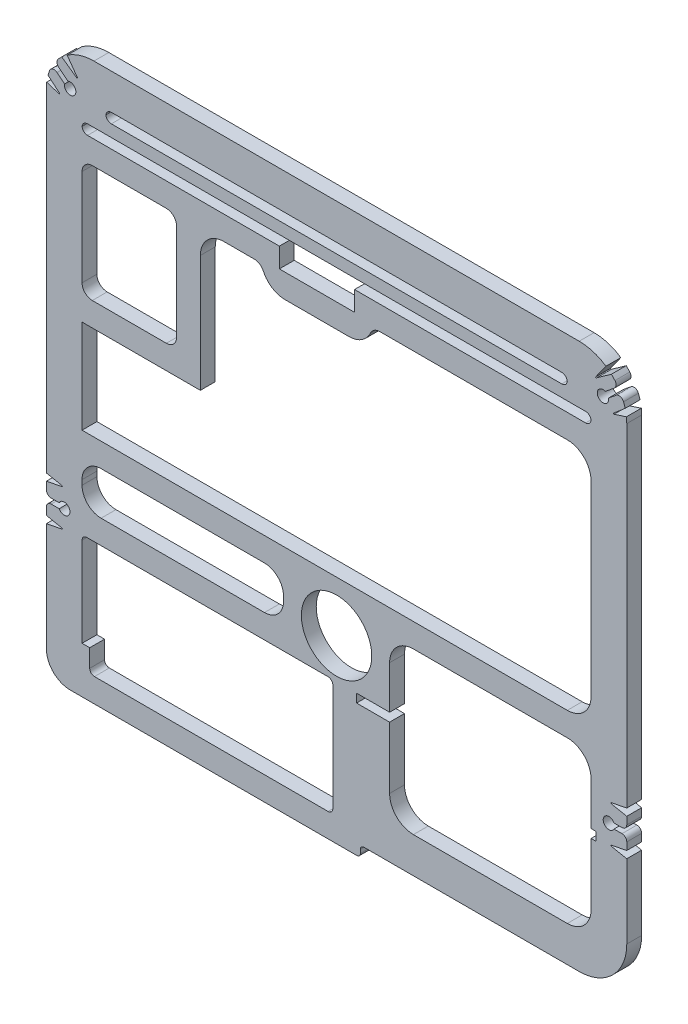
SolidWorks part; units mm, degrees
ref_plane "Front Plane" through (0, 0, 0) normal (0, 0, 1) x (1, 0, 0)
ref_plane "Top Plane" through (0, 0, 0) normal (0, 1, 0) x (1, 0, 0)
ref_plane "Right Plane" through (0, 0, 0) normal (1, 0, 0) x (0, 0, -1)
sketch "Sketch1" plane through (0, 0, 0) normal (0, 0, 1) x (1, 0, 0)
  line L0 (63.9883, 50.6392) -> (63.9883, 46.8292) construction
  line L1 (4.1102, -7.651) -> (66.0868, -7.651)
  line L2 (4.1102, -7.651) -> (4.1102, 50.6392)
  line L3 (4.1102, 50.6392) -> (66.0868, 50.6392)
  line L4 (66.0868, -7.651) -> (66.0868, 50.6392)
  line L5 (62.2768, 46.8292) -> (7.9202, 46.8292)
  line L6 (62.2768, 46.8292) -> (62.2768, -3.841)
  line L7 (62.2768, -3.841) -> (7.9202, -3.841)
  line L8 (7.9202, 46.8292) -> (7.9202, -3.841)
  line L9 (63.9883, 48.7342) -> (18.0707, 48.7342) construction
  line L10 (7.9202, 41.2855) -> (4.1102, 41.2855) construction
  line L11 (6.0152, 41.2855) -> (6.0152, 25.8577) construction
  line L12 (13.5248, -3.841) -> (13.5248, -7.651) construction
  line L13 (13.5248, -5.746) -> (21.1598, -5.746) construction
  line L14 (66.0868, 38.1916) -> (62.2768, 38.1916) construction
  line L15 (64.1818, 38.1916) -> (64.1818, 22.3321) construction
  line L16 (62.2768, 6.192) -> (62.2768, 41.7492) construction
  line L17 (7.9202, 36.7962) -> (7.9202, 1.239) construction
  line L22 (34.9556, 48.7342) -> (35.5018, 48.7342) construction
  line L23 (52.4244, -5.746) -> (51.8782, -5.746) construction
  dimension "D1" = 3.81
  dimension "D2" = 3.81
extrude "Boss-Extrude1" add sketch "Sketch1" along normal blind 1.5875
sketch "Sketch2" plane through (0, 0, 0) normal (0, 0, -1) x (-1, 0, 0)
  line L0 (-62.2768, -3.841) -> (-62.2768, 46.8292) construction
  line L1 (-62.2768, 15.868) -> (-7.9202, 15.868)
  line L2 (-62.2768, 15.868) -> (-62.2768, 13.328)
  line L3 (-62.2768, 13.328) -> (-7.9202, 13.328)
  line L4 (-7.9202, 15.868) -> (-7.9202, 13.328)
  line L5 (-7.9202, 46.8292) -> (-7.9202, -3.841) construction
  line L6 (-13.0532, 15.868) -> (-50.7532, 15.868) construction
  line L8 (-55.2788, 43.4256) -> (-16.9248, 43.4256) construction
  line L9 (-36.3812, 41.3174) -> (-29.6248, 41.3174) construction
  line L10 (-36.3812, 43.4256) -> (-36.3812, 41.3174) construction
  line L11 (-62.2768, 43.4256) -> (-37.0162, 43.4256)
  line L12 (-62.2768, 43.4256) -> (-62.2768, 40.8856)
  line L13 (-62.2768, 40.8856) -> (-38.9212, 40.8856)
  line L14 (-7.9202, 43.4256) -> (-7.9202, 40.8856)
  line L15 (-62.2768, 45.7624) -> (-7.9202, 45.7624)
  line L16 (-62.2768, 45.7624) -> (-62.2768, 44.4924)
  line L17 (-62.2768, 44.4924) -> (-7.9202, 44.4924)
  line L18 (-7.9202, 45.7624) -> (-7.9202, 44.4924)
  line L19 (-29.6248, 41.3174) -> (-29.6248, 43.4256) construction
  line L20 (-36.3812, 43.4256) -> (-36.3812, 41.3174) construction
  line L21 (-29.6248, 41.3174) -> (-29.6248, 43.4256) construction
  line L22 (-37.0162, 41.3174) -> (-37.0162, 43.4256)
  line L23 (-28.9898, 41.3174) -> (-37.0162, 41.3174)
  line L24 (-28.9898, 41.3174) -> (-28.9898, 43.4256)
  line L25 (-38.9212, 40.8856) -> (-38.9212, 38.7774)
  line L26 (-38.9212, 38.7774) -> (-27.0848, 38.7774)
  line L27 (-27.0848, 38.7774) -> (-27.0848, 40.8856)
  line L28 (-27.0848, 40.8856) -> (-7.9202, 40.8856)
  line L29 (-28.9898, 43.4256) -> (-7.9202, 43.4256)
  line L30 (-37.0162, 42.249) -> (-36.3812, 42.249) construction
  line L31 (-57.9086, 46.8292) -> (-57.9086, 45.7624) construction
  line L32 (-29.6248, 42.1673) -> (-28.9898, 42.1673) construction
  line L33 (-62.2768, 46.8292) -> (-7.9202, 46.8292) construction
  line L35 (-57.9086, 44.4924) -> (-57.9086, 43.4256) construction
  dimension "D1" = 2.54
  dimension "D2" = 1.905
  dimension "D3" = 2.54
  dimension "D4" = 1.905
  dimension "D5" = 1.27
  dimension "D6" = 0.635
extrude "Boss-Extrude2" add sketch "Sketch2" against normal up to surface (1.5875 mm away) up to face at (35.0985, 21.4941, 1.5875)
sketch "Sketch3" plane through (0, 0, 0) normal (0, 0, -1) x (-1, 0, 0)
  line L1 (-16.3032, 25.868) -> (-7.9202, 25.868) construction
  line L12 (-20.5532, 25.868) -> (-13.0532, 25.868)
  line L13 (-13.0532, 25.868) -> (-7.9202, 25.868)
  line L14 (-7.9202, 40.8856) -> (-7.9202, 15.868) construction
  line L15 (-7.9202, 25.868) -> (-7.9202, 28.408)
  line L16 (-7.9202, 28.408) -> (-18.0132, 28.408)
  line L17 (-18.0132, 28.408) -> (-18.0132, 40.8856)
  line L18 (-27.0848, 40.8856) -> (-7.9202, 40.8856) construction
  line L19 (-18.0132, 40.8856) -> (-20.5532, 40.8856)
  line L20 (-20.5532, 40.8856) -> (-20.5532, 25.868)
  line M27 (-27.0848, 40.8856) -> (-7.9202, 40.8856)
  line M28 (-7.9202, 40.8856) -> (-7.9202, 15.868)
  dimension "D3" = 2.54
  dimension "D4" = 2.54
extrude "Boss-Extrude3" add sketch "Sketch3" against normal up to surface (1.5875 mm away) contours L20 L12 L13 L16 L17 M27 M28 region at (20.3569, 33.3768, 0) up to face at (35.0985, 46.2958, 1.5875)
sketch "Sketch4" plane through (0, 0, 0) normal (0, 0, -1) x (-1, 0, 0)
  line L0 (-62.2768, 13.328) -> (-7.9202, 13.328) construction
  line L1 (-40.7627, 13.328) -> (-29.4343, 13.328)
  line L2 (-40.7627, 13.328) -> (-40.7627, -3.841)
  line L3 (-40.7627, -3.841) -> (-29.4343, -3.841)
  line L4 (-29.4343, 13.328) -> (-29.4343, -3.841)
  line L5 (-7.9202, -3.841) -> (-62.2768, -3.841) construction
  line L6 (-38.8577, 10.4578) -> (-40.7627, 10.4578) construction
  line L7 (-31.3393, 10.4578) -> (-29.4343, 10.4578) construction
  dimension "D1" = 1.905
extrude "Boss-Extrude4" add sketch "Sketch4" against normal up to surface (1.5875 mm away) up to face at (12.9667, 34.6468, 1.5875)
sketch "Sketch5" plane through (0, 0, 0) normal (0, 0, -1) x (-1, 0, 0)
  line L1 (-8.7364, -6.254) -> (-34.6952, -6.254) construction
  line L2 (-8.7364, -6.254) -> (-8.7364, 6.2047) construction
  line L6 (-8.7364, 6.2047) -> (-34.6952, 6.2047) construction
  line L7 (-34.6952, -6.254) -> (-34.6952, 6.2047) construction
  line L8 (-8.7364, -6.254) -> (-34.6952, -6.254)
  line L9 (-8.7364, -6.254) -> (-8.7364, 6.2047)
  line L10 (-8.7364, 6.2047) -> (-34.6952, 6.2047)
  line L11 (-34.6952, -6.254) -> (-34.6952, 6.2047)
  circle A1 centre (-35.0985, 10.4578) radius 3.7592 construction
  circle A2 centre (-35.0985, 10.4578) radius 3.7592
extrude "Cut-Extrude1" cut sketch "Sketch5" against normal up to surface (1.5875 mm away) up to face at (51.5197, 4.7435, 1.5875)
sketch "Sketch10" plane through (0, 0, 1.5875) normal (0, 0, 1) x (1, 0, 0)
  line L0 (29.4343, 13.328) -> (29.4343, 6.2047) construction
  line L1 (7.9202, 6.2047) -> (29.4343, 6.2047)
  line L2 (7.9202, 6.2047) -> (7.9202, 8.7447)
  line L3 (7.9202, 8.7447) -> (29.4343, 8.7447)
  line L4 (29.4343, 6.2047) -> (29.4343, 8.7447)
  line L5 (7.9202, 13.328) -> (7.9202, -3.841) construction
  line L6 (34.6952, 6.2047) -> (29.4343, 6.2047) construction
  dimension "D1" = 2.54
extrude "Boss-Extrude5" add sketch "Sketch10" against normal up to surface (1.5875 mm away) up to face at (20.1965, 2.3595, 0)
fillet "Fillet1" radius 5.08 3 edges at (66.0868, -7.651, 0.7937) (4.1102, 50.6392, 0.7937) (66.0868, 50.6392, 0.7937)
fillet "Fillet2" radius 2.54 5 edges at (20.5532, 40.8856, 0.7937) (27.0848, 38.7774, 0.7937) (62.2768, 40.8856, 0.7937) (62.2768, 15.868, 0.7937) (38.9212, 38.7774, 0.7937)
fillet "Fillet3" radius 1.0922 6 edges at (7.9202, 28.408, 0.7937) (18.0132, 28.408, 0.7937) (7.9202, 40.8856, 0.7937) (18.0132, 40.8856, 0.7937) (27.0848, 40.8856, 0.7937) (38.9212, 40.8856, 0.7937)
fillet "Fillet4" radius 0.5842 4 edges at (7.9202, 43.4256, 0.7937) (7.9202, 44.4924, 0.7937) (62.2768, 44.4924, 0.7937) (62.2768, 43.4256, 0.7937)
sketch "Sketch6" plane through (0, 0, 0) normal (0, 0, -1) x (-1, 0, 0)
  line L0 (-9.5532, 24.368) -> (-9.5532, 17.368) construction
  line L1 (-9.5532, 24.368) -> (-9.5532, 17.368)
  line L2 (-11.0532, 25.868) -> (-9.5532, 24.368) construction
  line L3 (-11.0532, 25.868) -> (-9.5532, 24.368)
  line L4 (-11.0532, 25.868) -> (-11.0532, 15.868)
  line L6 (-13.0532, 17.368) -> (-13.0532, 15.868)
  line L7 (-13.0532, 15.868) -> (-11.0532, 15.868)
  line L8 (-11.0532, 15.868) -> (-9.5532, 17.368)
  line L9 (-9.5532, 17.368) -> (-13.0532, 17.368)
  line L12 (-11.0532, 15.868) -> (-9.5532, 17.368)
  circle A0 centre (-63.5468, 46.8292) radius 0.6096 construction
  circle A1 centre (-6.6502, 46.8292) radius 0.6096 construction
  circle A2 centre (-64.1818, 7.6638) radius 0.6096 construction
  circle A3 centre (-6.0152, 7.6638) radius 0.6096 construction
  circle A4 centre (-63.5468, 46.8292) radius 0.6096
  circle A5 centre (-6.6502, 46.8292) radius 0.6096
  circle A6 centre (-64.1818, 7.6638) radius 0.6096
  circle A7 centre (-6.0152, 7.6638) radius 0.6096
  dimension "D1" = 0
extrude "Cut-Extrude2" cut sketch "Sketch6" against normal up to surface (1.5875 mm away) up to face at (17.1172, -1.2967, 1.5875)
sketch "Sketch9" plane through (0, 0, 1.5875) normal (0, 0, 1) x (1, 0, 0)
  line L4 (62.813, 6.2047) -> (37.2352, 6.2047)
  line L5 (37.2352, 6.2047) -> (37.2352, 5.2903)
  line L6 (37.2352, 5.2903) -> (62.813, 5.2903)
  line L7 (62.813, 5.2903) -> (62.813, 6.2047)
  line L8 (62.813, 6.2047) -> (37.2352, 6.2047)
  line L9 (37.2352, 6.2047) -> (37.2352, 5.2903)
  line L10 (37.2352, 5.2903) -> (62.813, 5.2903)
  line L11 (62.813, 5.2903) -> (62.813, 6.2047)
  dimension "D1" = 0
extrude "Cut-Extrude3" cut sketch "Sketch9" against normal up to surface (1.5875 mm away) up to face at (5.4056, 7.6638, 0)
fillet "Fillet6" radius 0.508 4 edges at (34.6952, 6.2047, 0.7937) (34.6952, -6.254, 0.7937) (8.7364, -6.254, 0.7937) (7.9202, 6.2047, 0.7937)
sketch "Sketch11" plane through (0, 0, 1.5875) normal (0, 0, 1) x (1, 0, 0)
  line L0 (9.2444, -6.254) -> (34.1872, -6.254) construction
  line L1 (4.1102, -7.651) -> (37.6385, -7.651)
  line L2 (4.1102, -7.651) -> (4.1102, -8.794)
  line L3 (4.1102, -8.794) -> (37.6385, -8.794)
  line L4 (37.6385, -7.651) -> (37.6385, -8.794)
  line L5 (35.0985, 14.217) -> (35.0985, -22.2214) construction
  circle A0 centre (35.0985, 10.4578) radius 3.7592 construction
  dimension "D1" = 2.54
  dimension "D2" = 2.54
extrude "Boss-Extrude6" add sketch "Sketch11" against normal up to surface (1.5875 mm away) up to face at (51.0212, 5.4129, 0)
fillet "Fillet7" radius 2.54 1 edges at (4.1102, -8.794, 0.7937)
fillet "Fillet8" radius 0.381 2 edges at (37.6385, -8.794, 0.7937) (37.6385, -7.651, 0.7937)
fillet "Fillet9" radius 2.032 4 edges at (29.4343, 8.7447, 0.7937) (29.4343, 13.328, 0.7937) (7.9202, 8.7447, 0.7937) (7.9202, 13.328, 0.7937)
fillet "Fillet10" radius 2.54 4 edges at (40.7627, -3.841, 0.7937) (62.2768, -3.841, 0.7937) (62.2768, 13.328, 0.7937) (40.7627, 13.328, 0.7937)
sketch "Sketch12" plane through (0, 0, 1.5875) normal (0, 0, 1) x (1, 0, 0)
  line L0 (7.9202, 46.8292) -> (7.9202, 45.7624) construction
  line L1 (7.9202, 46.8292) -> (10.4602, 46.8292)
  line L2 (7.9202, 46.8292) -> (7.9202, 45.7624)
  line L3 (7.9202, 45.7624) -> (10.4602, 45.7624)
  line L4 (10.4602, 46.8292) -> (10.4602, 45.7624)
  line L5 (62.2768, 46.8292) -> (7.9202, 46.8292) construction
  line L6 (62.2768, 45.7624) -> (7.9202, 45.7624) construction
  line L8 (62.2768, 46.8292) -> (59.7368, 46.8292)
  line L9 (62.2768, 46.8292) -> (62.2768, 45.7624)
  line L10 (62.2768, 45.7624) -> (59.7368, 45.7624)
  line L11 (59.7368, 46.8292) -> (59.7368, 45.7624)
  dimension "D1" = 2.54
extrude "Boss-Extrude7" add sketch "Sketch12" against normal up to surface (1.5875 mm away) up to face at (51.1458, 5.2455, 0)
fillet "Fillet11" radius 0.5842 4 edges at (59.7368, 45.7624, 0.7937) (59.7368, 46.8292, 0.7937) (10.4602, 45.7624, 0.7937) (10.4602, 46.8292, 0.7937)
sketch "Sketch13" plane through (0, 0, 1.5875) normal (0, 0, 1) x (1, 0, 0)
  line L0 (4.1471, 46.1706) -> (5.4628, 45.7479) construction
  line L1 (5.5112, 45.8349) -> (4.2848, 46.8798) construction
  line L2 (5.2504, 47.6106) -> (6.0537, 46.9553) construction
  line L3 (6.407, 47.3882) -> (5.4336, 48.1824) construction
  line L4 (5.7558, 49.3025) -> (7.3477, 48.1654) construction
  line L5 (7.4186, 48.2363) -> (6.3313, 49.7585) construction
  line L6 (6.6502, -8.794) -> (37.2575, -8.794)
  line L7 (37.6385, -8.413) -> (37.6385, -8.032)
  line L8 (38.0195, -7.651) -> (61.0068, -7.651)
  line L9 (66.0868, -2.571) -> (66.0868, 45.5592)
  line L10 (61.0068, 50.6392) -> (9.1902, 50.6392)
  line L11 (4.1102, 45.5592) -> (4.1102, -6.254)
  line L15 (66.0868, 5.3189) -> (66.0868, 6.0809)
  line L17 (4.1102, 10.0088) -> (4.1102, 9.2468)
  line L18 (4.1471, 46.1706) -> (5.4628, 45.7479)
  line L19 (5.5112, 45.8349) -> (4.2848, 46.8798)
  line L20 (5.2504, 47.6106) -> (6.0537, 46.9553)
  line L21 (6.407, 47.3882) -> (5.4336, 48.1824)
  line L22 (5.7558, 49.3025) -> (7.3477, 48.1654)
  line L23 (7.4186, 48.2363) -> (6.3313, 49.7585)
  line L24 (5.7661, 9.6776) -> (4.1102, 10.0088) construction
  line L25 (4.1102, 9.2468) -> (5.7661, 9.578) construction
  line L26 (5.4734, 7.9432) -> (4.6182, 7.9432) construction
  line L27 (4.6182, 7.3844) -> (5.4734, 7.3844) construction
  line L28 (5.7661, 5.7497) -> (4.1102, 6.0809) construction
  line L29 (4.1102, 5.3189) -> (5.7661, 5.6501) construction
  line L30 (5.7661, 9.6776) -> (4.1102, 10.0088)
  line L31 (4.1102, 9.2468) -> (5.7661, 9.578)
  line L32 (5.4734, 7.9432) -> (4.6182, 7.9432)
  line L33 (4.6182, 7.3844) -> (5.4734, 7.3844)
  line L34 (5.7661, 5.7497) -> (4.1102, 6.0809)
  line L35 (4.1102, 5.3189) -> (5.7661, 5.6501)
  line L36 (66.0868, 5.3189) -> (64.4308, 5.6501) construction
  line L37 (64.4308, 5.7497) -> (66.0868, 6.0809) construction
  line L38 (65.5788, 7.3844) -> (64.7236, 7.3844) construction
  line L39 (64.7236, 7.9432) -> (65.5788, 7.9432) construction
  line L40 (66.0868, 9.2468) -> (64.4308, 9.578) construction
  line L41 (64.4308, 9.6776) -> (66.0868, 10.0088) construction
  line L42 (66.0868, 5.3189) -> (64.4308, 5.6501)
  line L43 (64.4308, 5.7497) -> (66.0868, 6.0809)
  line L44 (65.5788, 7.3844) -> (64.7236, 7.3844)
  line L45 (64.7236, 7.9432) -> (65.5788, 7.9432)
  line L46 (66.0868, 9.2468) -> (64.4308, 9.578)
  line L47 (64.4308, 9.6776) -> (66.0868, 10.0088)
  line L48 (62.7783, 48.2363) -> (63.8656, 49.7585) construction
  line L49 (64.4411, 49.3025) -> (62.8492, 48.1654) construction
  line L50 (63.79, 47.3882) -> (64.7634, 48.1824) construction
  line L51 (64.9465, 47.6106) -> (64.1432, 46.9553) construction
  line L52 (64.6857, 45.8349) -> (65.9121, 46.8798) construction
  line L53 (66.0498, 46.1706) -> (64.7342, 45.7479) construction
  line L54 (62.7783, 48.2363) -> (63.8656, 49.7585)
  line L55 (64.4411, 49.3025) -> (62.8492, 48.1654)
  line L56 (63.79, 47.3882) -> (64.7634, 48.1824)
  line L57 (64.9465, 47.6106) -> (64.1432, 46.9553)
  line L58 (64.6857, 45.8349) -> (65.9121, 46.8798)
  line L59 (66.0498, 46.1706) -> (64.7342, 45.7479)
  line L60 (66.0868, -2.571) -> (66.0868, 45.5592) construction
  line L61 (66.0868, 5.3189) -> (66.0868, 10.0088)
  line L62 (66.0868, 9.2468) -> (66.0868, 10.0088)
  line L63 (66.0868, 6.8764) -> (66.0868, 8.4512)
  line L64 (4.1102, 45.5592) -> (4.1102, -6.254) construction
  line L65 (4.1102, 10.0088) -> (4.1102, 9.2468)
  line L66 (4.1102, 6.0809) -> (4.1102, 5.3189)
  line L67 (4.1102, 8.4512) -> (4.1102, 6.8764)
  line L68 (4.1102, 8.4512) -> (4.1102, 5.3189)
  arc A0 (5.4628, 45.7479) -> (5.5112, 45.8349) centre (5.4783, 45.7963) ccw construction
  arc A1 (5.2504, 47.6106) -> (4.4559, 47.4012) centre (4.9293, 47.217) ccw construction
  arc A2 (5.373, 48.9112) -> (5.4336, 48.1824) centre (5.7547, 48.576) ccw construction
  arc A3 (7.3477, 48.1654) -> (7.4186, 48.2363) centre (7.3772, 48.2068) ccw construction
  arc A4 (5.4628, 45.7479) -> (5.5112, 45.8349) centre (5.4783, 45.7963) ccw
  arc A5 (5.2504, 47.6106) -> (4.4559, 47.4012) centre (4.9293, 47.217) ccw
  arc A6 (37.2575, -8.794) -> (37.6385, -8.413) centre (37.2575, -8.413) ccw
  arc A7 (38.0195, -7.651) -> (37.6385, -8.032) centre (38.0195, -8.032) ccw
  arc A8 (61.0068, -7.651) -> (66.0868, -2.571) centre (61.0068, -2.571) ccw
  arc A9 (66.0868, 45.5592) -> (61.0068, 50.6392) centre (61.0068, 45.5592) ccw
  arc A10 (9.1902, 50.6392) -> (4.1102, 45.5592) centre (9.1902, 45.5592) ccw
  arc A11 (4.1102, -6.254) -> (6.6502, -8.794) centre (6.6502, -6.254) ccw
  arc A15 (66.0498, 46.1706) -> (65.9121, 46.8798) centre (61.0068, 45.5592) ccw
  arc A16 (6.3313, 49.7585) -> (5.7558, 49.3025) centre (9.1902, 45.5592) ccw
  arc A18 (5.373, 48.9112) -> (5.4336, 48.1824) centre (5.7547, 48.576) ccw
  arc A19 (7.3477, 48.1654) -> (7.4186, 48.2363) centre (7.3772, 48.2068) ccw
  arc A20 (5.7661, 9.578) -> (5.7661, 9.6776) centre (5.7561, 9.6278) ccw construction
  arc A21 (4.1102, 8.4512) -> (4.6182, 7.9432) centre (4.6182, 8.4512) ccw construction
  arc A22 (4.6182, 7.3844) -> (4.1102, 6.8764) centre (4.6182, 6.8764) ccw construction
  arc A23 (5.7661, 5.6501) -> (5.7661, 5.7497) centre (5.7561, 5.6999) ccw construction
  arc A24 (5.7661, 9.578) -> (5.7661, 9.6776) centre (5.7561, 9.6278) ccw
  arc A25 (4.1102, 8.4512) -> (4.6182, 7.9432) centre (4.6182, 8.4512) ccw
  arc A26 (4.6182, 7.3844) -> (4.1102, 6.8764) centre (4.6182, 6.8764) ccw
  arc A27 (5.7661, 5.6501) -> (5.7661, 5.7497) centre (5.7561, 5.6999) ccw
  arc A28 (64.4308, 5.7497) -> (64.4308, 5.6501) centre (64.4408, 5.6999) ccw construction
  arc A29 (66.0868, 6.8764) -> (65.5788, 7.3844) centre (65.5788, 6.8764) ccw construction
  arc A30 (65.5788, 7.9432) -> (66.0868, 8.4512) centre (65.5788, 8.4512) ccw construction
  arc A31 (64.4308, 9.6776) -> (64.4308, 9.578) centre (64.4408, 9.6278) ccw construction
  arc A32 (64.4308, 5.7497) -> (64.4308, 5.6501) centre (64.4408, 5.6999) ccw
  arc A33 (66.0868, 6.8764) -> (65.5788, 7.3844) centre (65.5788, 6.8764) ccw
  arc A34 (65.5788, 7.9432) -> (66.0868, 8.4512) centre (65.5788, 8.4512) ccw
  arc A35 (64.4308, 9.6776) -> (64.4308, 9.578) centre (64.4408, 9.6278) ccw
  arc A36 (62.7783, 48.2363) -> (62.8492, 48.1654) centre (62.8197, 48.2068) ccw construction
  arc A37 (64.7634, 48.1824) -> (64.8239, 48.9112) centre (64.4422, 48.576) ccw construction
  arc A38 (65.7411, 47.4012) -> (64.9465, 47.6106) centre (65.2676, 47.217) ccw construction
  arc A39 (64.6857, 45.8349) -> (64.7342, 45.7479) centre (64.7186, 45.7963) ccw construction
  arc A40 (62.7783, 48.2363) -> (62.8492, 48.1654) centre (62.8197, 48.2068) ccw
  arc A41 (64.7634, 48.1824) -> (64.8239, 48.9112) centre (64.4422, 48.576) ccw
  arc A42 (65.7411, 47.4012) -> (64.9465, 47.6106) centre (65.2676, 47.217) ccw
  arc A43 (64.6857, 45.8349) -> (64.7342, 45.7479) centre (64.7186, 45.7963) ccw
  arc A44 (66.0868, 45.5592) -> (61.0068, 50.6392) centre (61.0068, 45.5592) ccw construction
  circle A45 centre (63.5468, 46.8292) radius 0.6096 construction
  arc A46 (66.0498, 46.1706) -> (63.8656, 49.7585) centre (61.0068, 45.5592) ccw
  arc A47 (64.1432, 46.9553) -> (63.79, 47.3882) centre (63.5468, 46.8292) ccw
  arc A48 (64.4411, 49.3025) -> (63.8656, 49.7585) centre (61.0068, 45.5592) ccw
  arc A49 (65.7411, 47.4012) -> (64.8239, 48.9112) centre (61.0068, 45.5592) ccw
  circle A50 centre (64.1818, 7.6638) radius 0.6096 construction
  arc A51 (64.7236, 7.3844) -> (64.7236, 7.9432) centre (64.1818, 7.6638) ccw
  circle A52 centre (6.0152, 7.6638) radius 0.6096 construction
  arc A53 (5.4734, 7.9432) -> (5.4734, 7.3844) centre (6.0152, 7.6638) ccw
  arc A54 (5.373, 48.9112) -> (4.4559, 47.4012) centre (9.1902, 45.5592) ccw
  arc A55 (4.2848, 46.8798) -> (4.1471, 46.1706) centre (9.1902, 45.5592) ccw
  circle A56 centre (6.6502, 46.8292) radius 0.6096 construction
  arc A57 (6.407, 47.3882) -> (6.0537, 46.9553) centre (6.6502, 46.8292) ccw
  dimension "D1" = 0
extrude "Cut-Extrude4" cut sketch "Sketch13" against normal through all contours L22 A19 L23 A16 | A57 L21 A18 A54 A5 L20 | L19 A55 L18 A4 | L35 A27 L34 L66 | A53 L32 A25 L67 A26 L33 | L31 A24 L30 L17 | L43 A32 L42 L15 | A51 L44 A33 L61 A34 L45 | L47 A35 L46 L61 | L55 A46 L54 A40 | A47 L57 A42 A46 A41 L56 | L58 A43 L59 A15 region at (4.7305, 5.6999, 1.5875) region at (4.6977, 7.6638, 1.5875) region at (4.7305, 9.6278, 1.5875) region at (65.4665, 5.6999, 1.5875) region at (65.4992, 7.6638, 1.5875) region at (4.6929, 46.2513, 1.5875) region at (65.4665, 9.6278, 1.5875) region at (5.458, 47.7782, 1.5875) region at (6.5431, 49.0342, 1.5875) region at (65.504, 46.2513, 1.5875) region at (64.7389, 47.7782, 1.5875) region at (63.6538, 49.0342, 1.5875)
